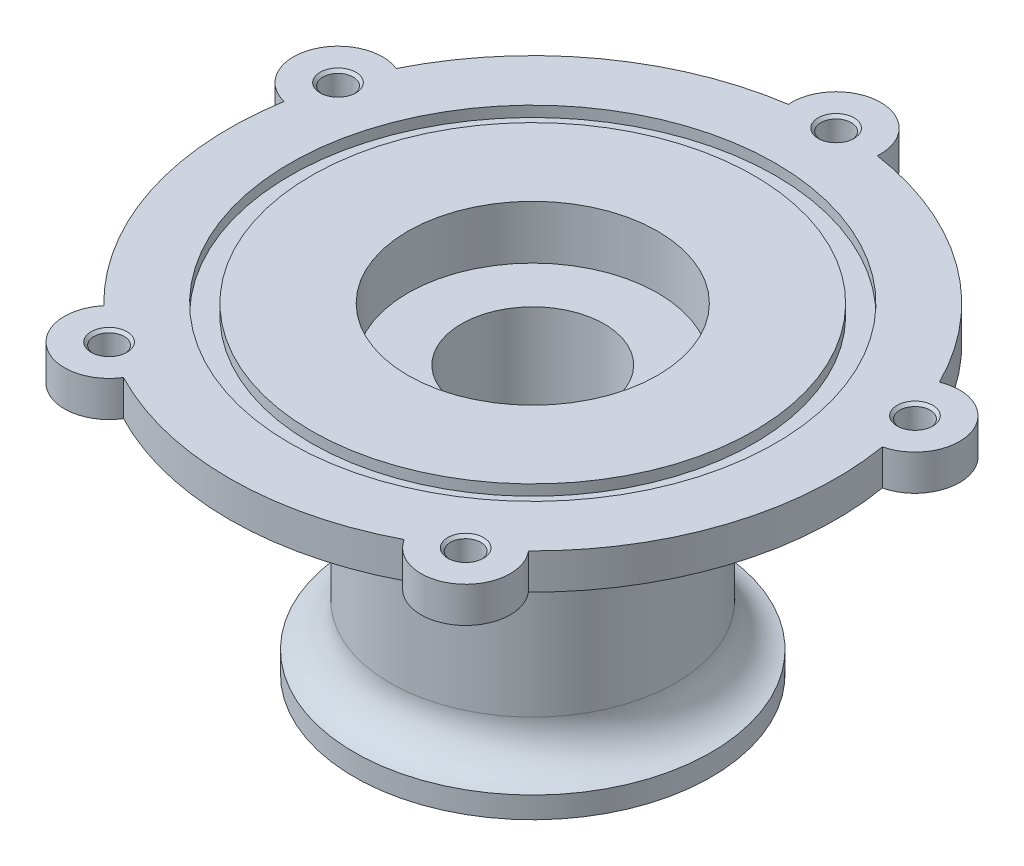
SolidWorks part; units mm, degrees
ref_plane "Front Plane" through (0, 0, 0) normal (0, 0, 1) x (1, 0, 0)
ref_plane "Top Plane" through (0, 0, 0) normal (0, 1, 0) x (1, 0, 0)
ref_plane "Right Plane" through (0, 0, 0) normal (1, 0, 0) x (0, 0, -1)
sketch "Sketch1" plane through (0, 0, 0) normal (0, 0, 1) x (1, 0, 0)
  line L0 (0, 0) -> (0, 90)
  line L1 (0, 90) -> (-85, 90)
  line L2 (-85, 90) -> (-85, 80)
  line L3 (-85, 80) -> (-40, 80)
  line L4 (-40, 80) -> (-40, 6)
  line L5 (-40, 6) -> (-50, 6)
  line L6 (-50, 6) -> (-50, 0)
  line L7 (-50, 0) -> (0, 0)
  dimension "D1" = 6
  dimension "D2" = 10
  dimension "D3" = 90
  dimension "D4" = 40
  dimension "D5" = 85
  dimension "D6" = 50
revolve "Revolve1" add sketch "Sketch1" angle 360 about L0
hole_wizard "Hole1" positions "Sketch2" profile "Sketch3" legacy end condition up to next
sketch "Sketch2" plane through (0, 90, 0) normal (0, 1, 0) x (1, 0, 0)
  point P0 (0, 0)
sketch "Sketch3" plane through (0, 90, 0) normal (1, 0, 0) x (0, 0, 1)
  line L0 (0, 0) -> (0, 90)
  line L1 (0, 90) -> (20, 90)
  line L2 (20, 90) -> (20, 15)
  line L3 (20, 15) -> (35, 15)
  line L4 (35, 15) -> (35, 0)
  line L5 (35, 0) -> (0, 0)
  line L6 (0, 110) -> (0, -10) construction
  dimension "Diameter" = 40
  dimension "Depth" = 90
  dimension "C-Bore Diameter" = 70
  dimension "C-Bore Depth" = 15
sketch "Sketch4" plane through (0, 90, 0) normal (0, 1, 0) x (1, 0, 0)
  circle A0 centre (0, 0) radius 62
  circle A1 centre (0, 0) radius 68
  dimension "D1" = 124
  dimension "D2" = 136
extrude "Cut-Extrude1" cut sketch "Sketch4" against normal blind 3
fillet "Fillet1" radius 21 1 edges at (0, 80, -40)
fillet "Fillet2" radius 12 1 edges at (0, 6, -40)
sketch "Sketch5" plane through (0, 90, 0) normal (0, 1, 0) x (1, 0, 0)
  line L0 (0, 0) -> (0, 85) construction
  circle A0 centre (0, 0) radius 85 construction
  arc A1 (12.4662, 84.0809) -> (-12.4662, 84.0809) centre (0, 85) ccw
  arc A2 (12.4662, 84.0809) -> (-12.4662, 84.0809) centre (0, 0) ccw
  dimension "D1" = 25
extrude "Boss-Extrude1" add sketch "Sketch5" against normal up to surface (10 mm away) up to face at (0, 80, 61)
pattern_circular "CirPattern1" count 5 over 360 about axis through (0, 0, 0) along (0, 1, 0) of "Boss-Extrude1"
hole_wizard "M10 Tapped Hole1" positions "Sketch6" profile "Sketch7" tap size "M10" standard "ISO"
sketch "Sketch6" plane through (0, 90, 0) normal (0, 1, 0) x (1, 0, 0)
  point P0 (49.9617, -68.7664)
  point P3 (-49.9617, -68.7664)
  point P6 (80.8398, 26.2664)
  point P9 (0, 85)
  point P12 (-80.8398, 26.2664)
sketch "Sketch7" plane through (49.9617, 90, 68.7664) normal (1, 0, 0) x (0, 0, 1)
  line L0 (0, 0) -> (0, 24.5)
  line L1 (0, 24.5) -> (4.25, 21.9463)
  line L2 (4.25, 21.9463) -> (4.25, 0.775)
  line L3 (4.25, 0.775) -> (5.025, 0)
  line L5 (5.025, 0) -> (0, 0)
  line L6 (-4.25, 0.775) -> (-5.025, 0) construction
  line L10 (0, 24.5) -> (-4.25, 21.9463) construction
  line L11 (0, -6.35) -> (0, 107.95) construction
  dimension "Tap Drill Dia." = 8.5
  dimension "Tap Drill Depth" = 24.5
  dimension "Near C'Sink Dia." = 10.05
  dimension "Near C'Sink Angle" = 90
  dimension "Drill Angle" = 118
cosmetic thread "Hole Thread1" parameters "D1"=20, "D2"=10
cosmetic thread "Hole Thread2" parameters "D1"=20, "D2"=10
cosmetic thread "Hole Thread3" parameters "D1"=20, "D2"=10
cosmetic thread "Hole Thread4" parameters "D1"=20, "D2"=10
cosmetic thread "Hole Thread5" parameters "D1"=20, "D2"=10
